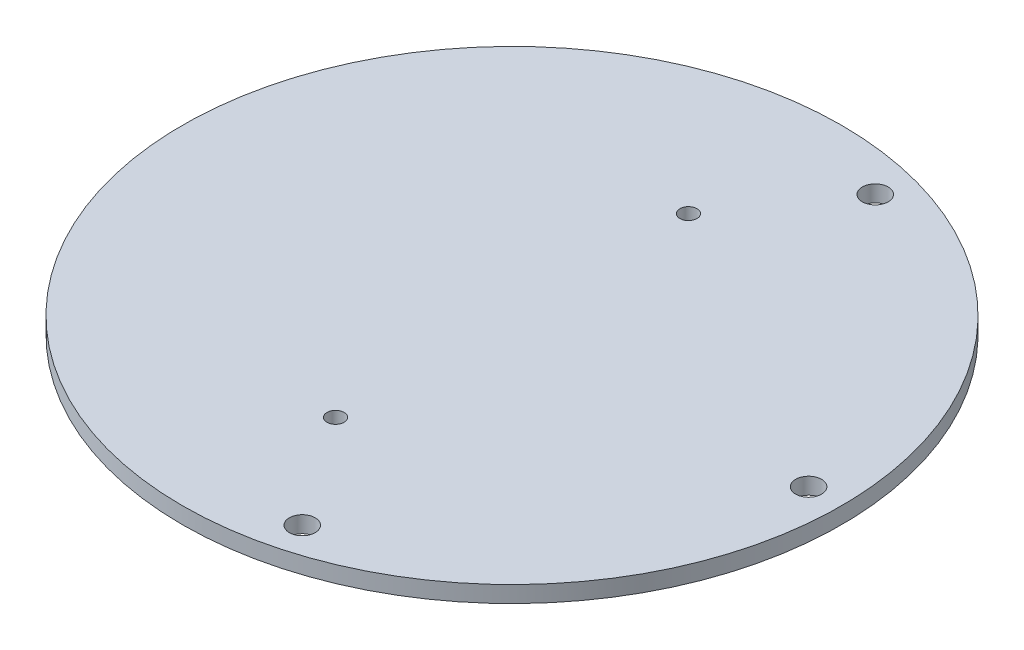
SolidWorks part; units mm, degrees
material "Plain Carbon Steel"
ref_plane "Front Plane" through (0, 0, 0) normal (0, 0, 1) x (1, 0, 0)
ref_plane "Top Plane" through (0, 0, 0) normal (0, 1, 0) x (1, 0, 0)
ref_plane "Right Plane" through (0, 0, 0) normal (1, 0, 0) x (0, 0, -1)
sketch "Sketch1" plane through (0, 0, 0) normal (0, 1, 0) x (1, 0, 0)
  circle A0 centre (0, 0) radius 63.5
  dimension "D1" = 127
extrude "Boss-Extrude1" add sketch "Sketch1" along normal blind 3.175
hole_wizard "Tap Drill for M4x0.7 Tap1" positions "Sketch6" profile "Sketch7" hole size "M4x0.7" standard "ANSI Metric" end condition through all
sketch "Sketch6" plane through (0, 3.175, 0) normal (0, 1, 0) x (1, 0, 0)
  line L0 (0, 34) -> (0, -34) construction
  point P1 (0, 34)
  point P2 (0, -34)
  point P5 (0, 0)
  dimension "D1" = 68
sketch "Sketch7" plane through (0, 3.175, -34) normal (1, 0, 0) x (0, 0, 1)
  line L0 (0, 0) -> (0, 3.175)
  line L1 (0, 3.175) -> (1.65, 3.175)
  line L2 (1.65, 3.175) -> (1.65, 0)
  line L5 (1.65, 0) -> (0, 0)
  line L11 (0, -6.35) -> (0, 107.95) construction
  dimension "Thru Hole Dia." = 3.3
  dimension "Thru Hole Depth" = 3.175
sketch "Sketch8" plane through (0, 3.175, 0) normal (0, 1, 0) x (1, 0, 0)
  line L0 (14.7915, 55.2027) -> (0, 0) construction
  line L1 (0, 0) -> (14.7915, -55.2027) construction
  line L2 (0, 0) -> (57.15, 0) construction
  point P0 (57.15, 0)
  point P1 (14.7915, 55.2027)
  point P2 (14.7915, -55.2027)
  dimension "D1" = 75
  dimension "D2" = 75
  dimension "D3" = 57.15
sketch "Sketch11" plane through (0, 3.175, 0) normal (0, 1, 0) x (1, 0, 0)
  point P0 (14.7915, 55.2027)
  point P3 (57.15, 0)
  point P6 (14.7915, -55.2027)
hole_wizard "#9 (0.196) Diameter Hole1" positions "Sketch11" profile "Sketch10" hole size "#9" standard "ANSI Inch" end condition through all
sketch "Sketch10" plane through (14.7915, 3.175, -55.2027) normal (1, 0, 0) x (0, 0, 1)
  line L0 (0, 0) -> (0, 3.175)
  line L1 (0, 3.175) -> (2.4892, 3.175)
  line L2 (2.4892, 3.175) -> (2.4892, 0)
  line L5 (2.4892, 0) -> (0, 0)
  line L11 (0, -6.35) -> (0, 107.95) construction
  dimension "Thru Hole Dia." = 4.9784
  dimension "Thru Hole Depth" = 3.175
equation "\"mount distance\"= 2.25"
equation "\"D3@Sketch8\"=\"mount distance\""
